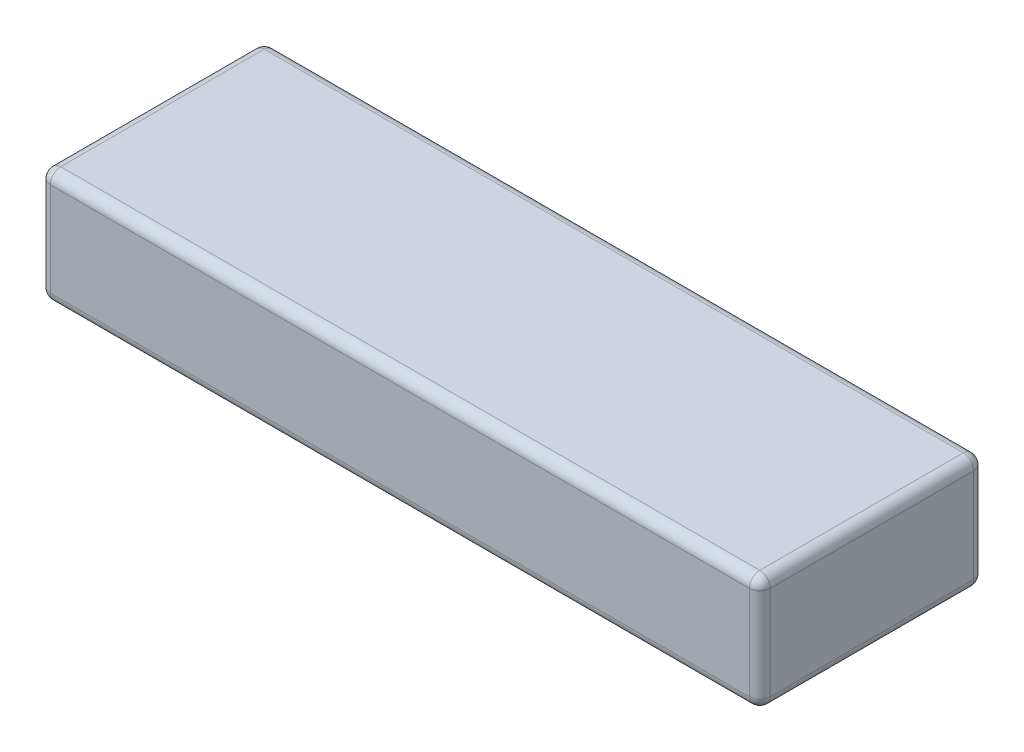
SolidWorks part; units mm, degrees
ref_plane "Ebene vorne" through (0, 0, 0) normal (0, 0, 1) x (1, 0, 0)
ref_plane "Ebene oben" through (0, 0, 0) normal (0, 1, 0) x (1, 0, 0)
ref_plane "Ebene rechts" through (0, 0, 0) normal (1, 0, 0) x (0, 0, -1)
sketch "Skizze1" plane through (0, 0, 0) normal (0, 1, 0) x (1, 0, 0)
  line L1 (-69, -21.5) -> (69, -21.5)
  line L2 (-69, -21.5) -> (-69, 21.5)
  line L3 (-69, 21.5) -> (69, 21.5)
  line L4 (69, -21.5) -> (69, 21.5)
  line L5 (-69, -21.5) -> (69, 21.5) construction
  line L6 (-69, 21.5) -> (69, -21.5) construction
  point P0 (0, 0)
  dimension "D1" = 138
  dimension "D2" = 43
extrude "Grundkoerper" add sketch "Skizze1" along normal blind 22
fillet "Verrundung1" radius 2 12 edges at (69, 0, 0) (0, 0, -21.5) (-69, 0, 0) (0, 0, 21.5) (-69, 11, 21.5) (-69, 11, -21.5) (69, 11, -21.5) (69, 11, 21.5) (69, 22, 0) (0, 22, -21.5) (-69, 22, 0) (0, 22, 21.5)
sketch "Skizze2" plane through (69, 0, 0) normal (1, 0, 0) x (0, 0, -1)
  line L0 (19.5, 11) -> (-19.5, 11) construction
  line L1 (19.5, 2) -> (19.5, 20) construction
  line L2 (-19.5, 20) -> (-19.5, 2) construction
  line L3 (19.5, 0) -> (-19.5, 0) construction
  point P6 (-18.25, 10)
  point P7 (-18.25, 5)
  point P8 (18.25, 12)
  point P9 (18.25, 10)
  point P10 (18.25, 8)
  point P12 (18.25, 14)
  dimension "D1" = 5
  dimension "D2" = 1.25
  dimension "D3" = 2
  dimension "D4" = 2
  dimension "D5" = 1.25
  dimension "D6" = 5
sketch "0_0_Point" plane through (69, 0, 0) normal (1, 0, 0) x (0, 0, -1)
  point P0 (-18.25, 10)
other "0_0" parameters "Durchmesser"=2, "Stumpflänge"=2
ref_axis "Achse1" through (79, 10, 18.25) along (-1, 0, 0)
sketch "0_1_Point" plane through (69, 0, 0) normal (1, 0, 0) x (0, 0, -1)
  point P0 (-18.25, 5)
other "0_1" parameters "Durchmesser"=2, "Stumpflänge"=2
ref_axis "Achse2" through (79, 5, 18.25) along (-1, 0, 0)
sketch "1_0_Point" plane through (69, 0, 0) normal (1, 0, 0) x (0, 0, -1)
  point P0 (18.25, 8)
other "1_0" parameters "Durchmesser"=2, "Stumpflänge"=2
ref_axis "Achse3" through (79, 8, -18.25) along (-1, 0, 0)
sketch "1_1_Point" plane through (69, 0, 0) normal (1, 0, 0) x (0, 0, -1)
  point P0 (18.25, 10)
other "1_1" parameters "Durchmesser"=2, "Stumpflänge"=2
ref_axis "Achse4" through (79, 10, -18.25) along (-1, 0, 0)
sketch "1_2_Point" plane through (69, 0, 0) normal (1, 0, 0) x (0, 0, -1)
  point P0 (18.25, 12)
other "1_2" parameters "Durchmesser"=2, "Stumpflänge"=2
ref_axis "Achse5" through (79, 12, -18.25) along (-1, 0, 0)
sketch "1_3_Point" plane through (69, 0, 0) normal (1, 0, 0) x (0, 0, -1)
  point P0 (18.25, 14)
other "1_3" parameters "Durchmesser"=2, "Stumpflänge"=2
ref_axis "Achse6" through (79, 14, -18.25) along (-1, 0, 0)
